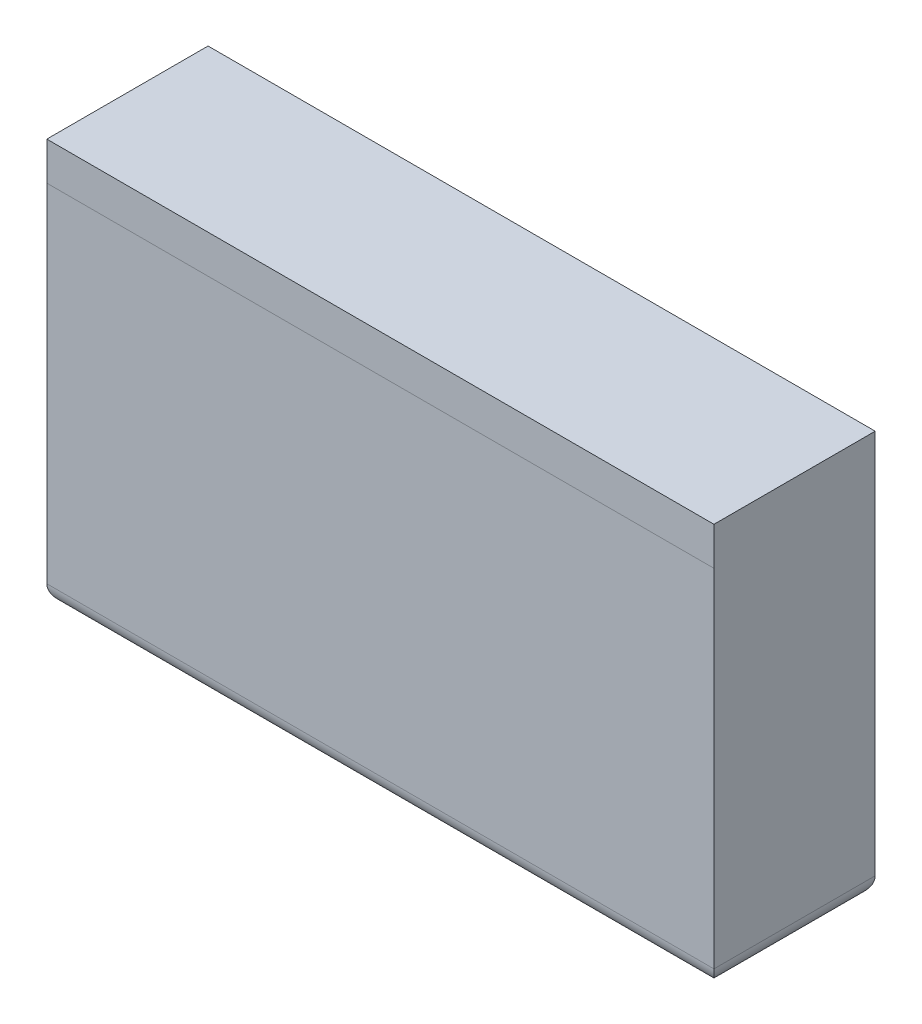
SolidWorks part; units mm, degrees
material "ABS PC"
ref_plane "Front Plane" through (0, 0, 0) normal (0, 0, 1) x (1, 0, 0)
ref_plane "Top Plane" through (0, 0, 0) normal (0, 1, 0) x (1, 0, 0)
ref_plane "Right Plane" through (0, 0, 0) normal (1, 0, 0) x (0, 0, -1)
sketch "Sketch1" plane through (0, 0, 0) normal (0, 1, 0) x (1, 0, 0)
  line L0 (-48.1771, 17.15) -> (118.8229, 17.15)
  line L1 (-52.1771, -21.15) -> (122.8229, -21.15)
  line L2 (-52.1771, -21.15) -> (-52.1771, 21.15)
  line L3 (-52.1771, 21.15) -> (122.8229, 21.15)
  line L4 (122.8229, -21.15) -> (122.8229, 21.15)
  line L5 (-52.1771, -21.15) -> (122.8229, 21.15) construction
  line L6 (-52.1771, 21.15) -> (122.8229, -21.15) construction
  line L7 (118.8229, -17.15) -> (118.8229, 17.15)
  line L8 (-48.1771, -17.15) -> (118.8229, -17.15)
  line L9 (-48.1771, -17.15) -> (-48.1771, 17.15)
  circle A0 centre (-32.1771, 0) radius 5
  circle A1 centre (102.8229, 0) radius 5
  point P0 (0, 0)
  dimension "D4" = 20
  dimension "D1" = 42.3
  dimension "D2" = 175
  dimension "D5" = 20
  dimension "D3" = 4
extrude "Boss-Extrude1" add sketch "Sketch1" along normal blind 4 contours L9 L8 L7 L0 A1 A0 | L1 L4 L3 L2 L8 L9 L0 L7 | A1 | A0 region at (35.3229, 0, 0) region at (-50.3767, 0, 0) region at (102.8229, 0, 0)
extrude "Boss-Extrude2" add sketch "Sketch1<3>" along normal blind 96 contours L1 L4 L3 L2 L8 L9 L0 L7 region at (-50.3767, 0, 0)
sketch "Sketch1<3>" plane through (0, 0, 0) normal (0, 1, 0) x (1, 0, 0) same geometry as "Sketch1"
extrude "Boss-Extrude3" add sketch "Sketch1<4>" against normal blind 10 contours A0 | A1 region at (-32.1771, 0, 0)
sketch "Sketch1<4>" plane through (0, 0, 0) normal (0, 1, 0) x (1, 0, 0) same geometry as "Sketch1"
fillet "Fillet1" radius 5 4 edges at (35.3229, 0, 21.15) (-52.1771, 0, 0) (35.3229, 0, -21.15) (122.8229, 0, 0)
sketch "Sketch3" plane through (0, 0, -21.15) normal (0, 0, -1) x (-1, 0, 0)
  line L0 (-35.3229, 5) -> (-35.3229, 16.03) construction
  line L1 (4.0421, 16.03) -> (-74.6879, 16.03)
  line L2 (-74.6879, 16.03) -> (-74.6879, 5)
  line L3 (-74.6879, 5) -> (4.0421, 5)
  line L4 (4.0421, 16.03) -> (4.0421, 5)
  dimension "D1" = 39.365
extrude "Cut-Extrude1" cut sketch "Sketch3" against normal blind 4
sketch "Sketch4" plane through (0, 96, 0) normal (0, 1, 0) x (1, 0, 0)
  line L1 (-52.1757, 21.1487) -> (122.8229, 21.1487)
  line L2 (-52.1757, 21.1487) -> (-52.1757, -21.1487)
  line L3 (-52.1757, -21.1487) -> (122.8229, -21.1487)
  line L4 (122.8229, 21.1487) -> (122.8229, -21.1487)
  line L5 (-48.1771, 17.15) -> (118.8229, 17.15)
  line L6 (-48.1771, 17.15) -> (-48.1771, -17.15)
  line L7 (-48.1771, -17.15) -> (118.8229, -17.15)
  line L8 (118.8229, 17.15) -> (118.8229, -17.15)
extrude "Boss-Extrude4" add sketch "Sketch4" along normal blind 10 contours L2 L3 L4 L1
